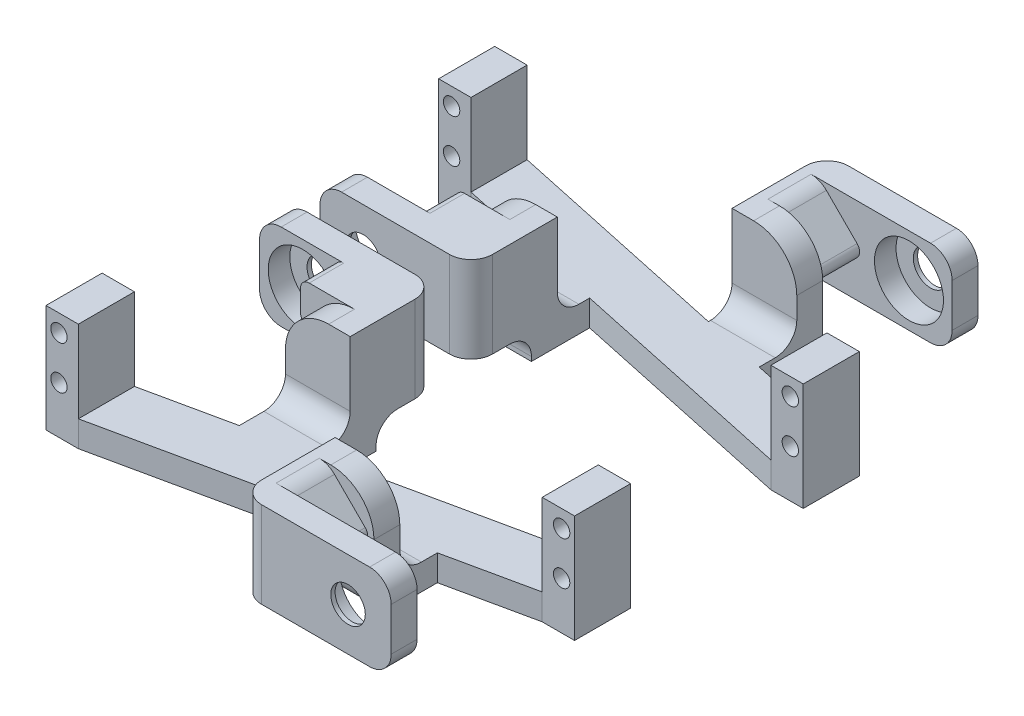
SolidWorks part; units mm, degrees
ref_plane "Front Plane" through (0, 0, 0) normal (0, 0, 1) x (1, 0, 0)
ref_plane "Top Plane" through (0, 0, 0) normal (0, 1, 0) x (1, 0, 0)
ref_plane "Right Plane" through (0, 0, 0) normal (1, 0, 0) x (0, 0, -1)
sketch "Sketch1" plane through (0, 0, 0) normal (0, 1, 0) x (1, 0, 0)
  line L0 (0, -1000) -> (0, 49000) construction
  line L1 (-10, 0) -> (10, 0)
  line L2 (-10, 0) -> (-10, -39.4362)
  line L3 (-10, -39.4362) -> (10, -39.4362)
  line L4 (10, 0) -> (10, -39.4362)
  line L5 (0, 0) -> (12, -20.7846) construction
  line L7 (10, -10) -> (16.9706, -16.9706)
  circle A0 centre (0, 0) radius 24
  dimension "D1" = 48
  dimension "D2" = 20
  dimension "D3" = 10
  dimension "D4" = 135
  dimension "D6" = 150
sketch "Sketch2" plane through (0, 0, 0) normal (0, 1, 0) x (1, 0, 0)
  line L0 (-995.7415, 0) -> (48791.3311, 0) construction
  line L1 (-36.75, 13) -> (51.75, 32)
  line L2 (51.75, 19) -> (59.25, 19)
  line L3 (51.75, 19) -> (51.75, 32) construction
  line L4 (51.75, 32) -> (59.25, 32)
  line L5 (59.25, 19) -> (59.25, 32)
  line L6 (-44.25, 0) -> (-36.75, 0)
  line L7 (-44.25, 0) -> (-44.25, 13)
  line L8 (-44.25, 13) -> (-36.75, 13)
  line L9 (-36.75, 0) -> (-36.75, 13) construction
  line L10 (59.25, 19) -> (3.75, 19) construction
  line L11 (59.25, 19) -> (59.25, 16) construction
  line L12 (59.25, 16) -> (3.75, 16) construction
  line L13 (3.75, 19) -> (3.75, 16) construction
  line L14 (-44.25, 13) -> (11.25, 13) construction
  line L15 (-44.25, 13) -> (-44.25, 16) construction
  line L16 (-44.25, 16) -> (11.25, 16) construction
  line L17 (11.25, 13) -> (11.25, 16) construction
  line L18 (-36.75, 0) -> (51.75, 19)
  dimension "D1" = 7.5
  dimension "D2" = 7.5
  dimension "D3" = 13
  dimension "D4" = 13
  dimension "D5" = 3
  dimension "D6" = 3
  dimension "D7" = 55.5
  dimension "D8" = 55.5
  dimension "D9" = 7.5
  dimension "D10" = 3.75
  dimension "D11" = 88.5
extrude "Boss-Extrude1" add sketch "Sketch2" along normal blind 6
sketch "Sketch3" plane through (0, 6, 0) normal (0, 1, 0) x (1, 0, 0)
  line L1 (-44.25, 13) -> (-36.75, 13)
  line L2 (-44.25, 13) -> (-44.25, 0)
  line L3 (-44.25, 0) -> (-36.75, 0)
  line L4 (-36.75, 13) -> (-36.75, 0)
  line L5 (59.25, 32) -> (51.75, 32)
  line L6 (59.25, 32) -> (59.25, 19)
  line L7 (59.25, 19) -> (51.75, 19)
  line L8 (51.75, 32) -> (51.75, 19)
extrude "Boss-Extrude2" add sketch "Sketch3" along normal blind 19
sketch "Sketch4" plane through (0, 0, 0) normal (0, 0, 1) x (1, 0, 0)
  line L0 (-36.75, 6) -> (51.75, 6) construction
  line L1 (-36.75, 25) -> (-36.75, 6) construction
  line L2 (-36.75, 25) -> (-36.75, 6)
  line L3 (-36.75, 6) -> (51.75, 6)
  line L4 (51.75, 6) -> (51.75, 25)
  line L5 (7.5, 6) -> (7.5, 25) construction
  circle A0 centre (-41.25, 11) radius 1.9
  circle A1 centre (-41.25, 21) radius 1.9
  circle A2 centre (56.25, 11) radius 1.9
  circle A3 centre (56.25, 21) radius 1.9
  dimension "D1" = 3.8
  dimension "D2" = 3.8
  dimension "D3" = 5
  dimension "D4" = 10
  dimension "D6" = 4.5
extrude "Cut-Extrude1" cut sketch "Sketch4" against normal through all contours A1 | A0 | A3 | A2 region at (-41.25, 11, 0) region at (-41.25, 21, 0) region at (56.25, 21, 0)
mirror "Mirror1" about plane through (0, 0, 0) normal (0, 0, 1) of bodies 103
delete or keep bodies "Body-Delete/Keep 1" type delete bodies bodies 103
sketch "Sketch5" plane through (0, 0, 0) normal (0, 1, 0) x (1, 0, 0)
  line L0 (-36.75, 0) -> (51.75, -19) construction
  line L1 (16.75, -11.4859) -> (31.75, -14.7062)
  line L2 (51.75, -32) -> (51.75, -19) construction
  line L4 (16.75, -11.4859) -> (16.75, 0)
  line L5 (16.75, 0) -> (31.75, 0)
  line L6 (31.75, -14.7062) -> (31.75, 0)
  line L7 (51.75, -19) -> (59.25, -19) construction
  dimension "D1" = 15
  dimension "D2" = 20
  dimension "D3" = 19
extrude "Boss-Extrude3" add sketch "Sketch5" along normal up to surface (6 mm away) up to face at (7.5, 6, 16)
sketch "Sketch7" plane through (0, 6, 0) normal (0, 1, 0) x (1, 0, 0)
  line L0 (31.75, -14.7062) -> (31.75, 0) construction
  line L1 (16.75, 0) -> (31.75, 0)
  line L2 (16.75, 0) -> (16.75, -6)
  line L3 (16.75, -6) -> (31.75, -6)
  line L4 (31.75, 0) -> (31.75, -6)
  dimension "D1" = 6
extrude "Boss-Extrude4" add sketch "Sketch7" along normal blind 20
sketch "Sketch9" plane through (0, 6, 0) normal (0, 1, 0) x (1, 0, 0)
  line L0 (41.75, -1034.9088) -> (41.75, 48965.0912) construction
  line L1 (51.75, -32) -> (51.75, -19) construction
  line L3 (31.75, 16) -> (51.75, 16)
  line L4 (31.75, 16) -> (31.75, 10)
  line L5 (31.75, 10) -> (51.75, 10)
  line L6 (51.75, 16) -> (51.75, 10)
  dimension "D1" = 10
  dimension "D2" = 20
  dimension "D3" = 10
  dimension "D4" = 29
  dimension "D5" = 6
extrude "Boss-Extrude5" add sketch "Sketch9" along normal blind 20 separate body
sketch "Sketch10" plane through (0, 0, -10) normal (0, 0, 1) x (1, 0, 0)
  line L0 (51.75, 6) -> (-36.75, 6) construction
  line L1 (51.75, 26) -> (51.75, 6) construction
  circle A0 centre (41.75, 16) radius 8
  circle A1 centre (41.75, 16) radius 4
  dimension "D1" = 16
  dimension "D4" = 8
  dimension "D2" = 10
  dimension "D3" = 10
extrude "Cut-Extrude2" cut sketch "Sketch10" against normal blind 5
extrude "Cut-Extrude3" cut sketch "Sketch10<2>" against normal blind 15 contours A1 region at (41.75, 16, -10)
sketch "Sketch10<2>" plane through (0, 0, -10) normal (0, 0, 1) x (1, 0, 0) same geometry as "Sketch10"
sketch "Sketch11" plane through (0, 0, -10) normal (0, 0, 1) x (1, 0, 0)
  line L0 (-958.25, 16) -> (31.1434, 16) construction
  line L4 (29.7292, 14.5858) -> (22.6079, 7.4645)
  line L5 (19.0723, 26) -> (16.75, 26)
  line L7 (19.0723, 6) -> (16.75, 6)
  line L8 (16.75, 26) -> (16.75, 6)
  line L9 (29.7292, 17.4142) -> (22.6079, 24.5355)
  line L11 (41.75, 16) -> (49041.75, 16) construction
  circle A0 centre (41.75, 16) radius 24 construction
  arc A2 (22.6079, 7.4645) -> (19.0723, 6) centre (19.0723, 11) cw
  arc A3 (22.6079, 24.5355) -> (19.0723, 26) centre (19.0723, 21) ccw
  arc A4 (29.7292, 14.5858) -> (29.7292, 17.4142) centre (28.315, 16) ccw
  line M9 (31.75, 26) -> (31.75, 6)
  dimension "D1" = 48
  dimension "D2" = 5
  dimension "D3" = 2
  dimension "D4" = 7.5
extrude "Boss-Extrude6" add sketch "Sketch11" along normal up to surface (16 mm away) contours L5 L8 L7 M9 | L5 L8 L7 A2 L4 A4 L9 A3 region at (21.8555, 16, -10) up to face at (24.25, 16, 6)
sketch "Sketch12" plane through (0, 0, -10) normal (0, 0, -1) x (-1, 0, 0)
  line L1 (-31.75, 26) -> (-16.75, 26)
  line L2 (-31.75, 26) -> (-31.75, 6)
  line L3 (-31.75, 6) -> (-16.75, 6)
  line L4 (-16.75, 26) -> (-16.75, 6)
extrude "Boss-Extrude7" add sketch "Sketch12" along normal up to surface (6 mm away) up to face at (45.75, 16, -16)
sketch "Sketch13" plane through (0, 0, 0) normal (0, 1, 0) x (1, 0, 0)
  line L0 (-36.75, 0) -> (-36.75, -13) construction
  line L1 (-16.75, 0) -> (-1.75, 0)
  line L2 (-16.75, 0) -> (-16.75, -48)
  line L3 (-16.75, -48) -> (-1.75, -48)
  line L4 (-1.75, 0) -> (-1.75, -48)
  line L5 (-44.25, 0) -> (-36.75, 0) construction
  line L6 (-36.75, -13) -> (-44.25, -13) construction
  line L7 (-16.75, -17.2938) -> (-1.75, -20.5141)
  line L8 (-16.75, -48) -> (-52.4842, -48)
  line L9 (-16.75, -48) -> (-16.75, -42)
  line L10 (-16.75, -42) -> (-52.4842, -42)
  line L11 (-52.4842, -48) -> (-52.4842, -42)
  line L12 (-1.75, -34) -> (-52.4842, -34)
  line L13 (-16.75, -34) -> (-52.4842, -34) construction
  dimension "D1" = 15
  dimension "D2" = 20
  dimension "D3" = 35
  dimension "D4" = 6
  dimension "D5" = 8
extrude "Boss-Extrude8" add sketch "Sketch13" along normal up to surface (6 mm away) contours L12 L4 L7 L2 region at (-9.5167, 0, 26.4234)
sketch "Sketch14" plane through (0, 6, 0) normal (0, 1, 0) x (1, 0, 0)
  line L0 (-1.75, 0) -> (-1.75, -48) construction
  line L1 (-16.75, -34) -> (-1.75, -34)
  line L2 (-16.75, -34) -> (-16.75, -28)
  line L3 (-16.75, -28) -> (-1.75, -28)
  line L4 (-1.75, -34) -> (-1.75, -28)
  dimension "D1" = 6
extrude "Boss-Extrude9" add sketch "Sketch14" along normal blind 20
sketch "Sketch15" plane through (0, 0, 34) normal (0, 0, 1) x (1, 0, 0)
  line L0 (-36.75, 25) -> (-36.75, 6) construction
  line L1 (-26.75, -984) -> (-26.75, 49016)
  line L2 (-19.25, 8) -> (-19.25, 13.2161)
  line L3 (-1.75, 26) -> (-17.25, 26)
  line L4 (-1.75, 6) -> (-17.25, 6)
  line L6 (-1.75, 6) -> (-1.75, 26)
  line L7 (-19.25, 18.7839) -> (-19.25, 24)
  circle A0 centre (-26.75, 16) radius 4 construction
  arc A1 (-19.25, 13.2161) -> (-19.25, 18.7839) centre (-26.75, 16) ccw
  circle A2 centre (-41.25, 21) radius 1.9 construction
  arc A4 (-19.25, 8) -> (-17.25, 6) centre (-17.25, 8) ccw
  arc A5 (-17.25, 26) -> (-19.25, 24) centre (-17.25, 24) ccw
  dimension "D1" = 16
  dimension "D2" = 8
  dimension "D4" = 10
  dimension "D7" = 2
  dimension "D3" = 5
  dimension "D5" = 7.5
  dimension "D6" = 6
extrude "Boss-Extrude10" add sketch "Sketch15" along normal blind 8
sketch "Sketch16" plane through (0, 0, 42) normal (0, 0, 1) x (1, 0, 0)
  line L1 (-1.75, 26) -> (-36.75, 26)
  line L2 (-1.75, 26) -> (-1.75, 6)
  line L3 (-1.75, 6) -> (-36.75, 6)
  line L4 (-36.75, 26) -> (-36.75, 6)
  circle A0 centre (-26.75, 16) radius 8
  circle A1 centre (-41.25, 21) radius 1.9 construction
  dimension "D3" = 16
  dimension "D4" = 5
  dimension "D1" = 35
  dimension "D2" = 20
  dimension "D5" = 10
extrude "Boss-Extrude11" add sketch "Sketch16" along normal blind 6
sketch "Sketch18" plane through (0, 0, 48) normal (0, 0, 1) x (1, 0, 0)
  circle A0 centre (-26.75, 16) radius 8
  circle A1 centre (-26.75, 16) radius 4
  dimension "D1" = 8
  dimension "D2" = 16
extrude "Boss-Extrude12" add sketch "Sketch18" against normal blind 1
fillet "Fillet1" radius 10 2 edges at (31.75, 26, 3) (-16.75, 26, 31)
fillet "Fillet2" radius 5 10 edges at (51.75, 6, -13) (51.75, 26, -13) (16.75, 16, -16) (24.25, 6, 6) (24.25, 0, 0) (-9.25, 6, 34) (-9.25, 6, 28) (-1.75, 16, 48) (-36.75, 6, 45) (-36.75, 26, 45)
ref_plane "Plane1" through (0, 0, 52) normal (0, 0, 1) x (1, 0, 0)
mirror "Mirror3" about plane through (0, 0, 52) normal (0, 0, 1) of bodies 116
